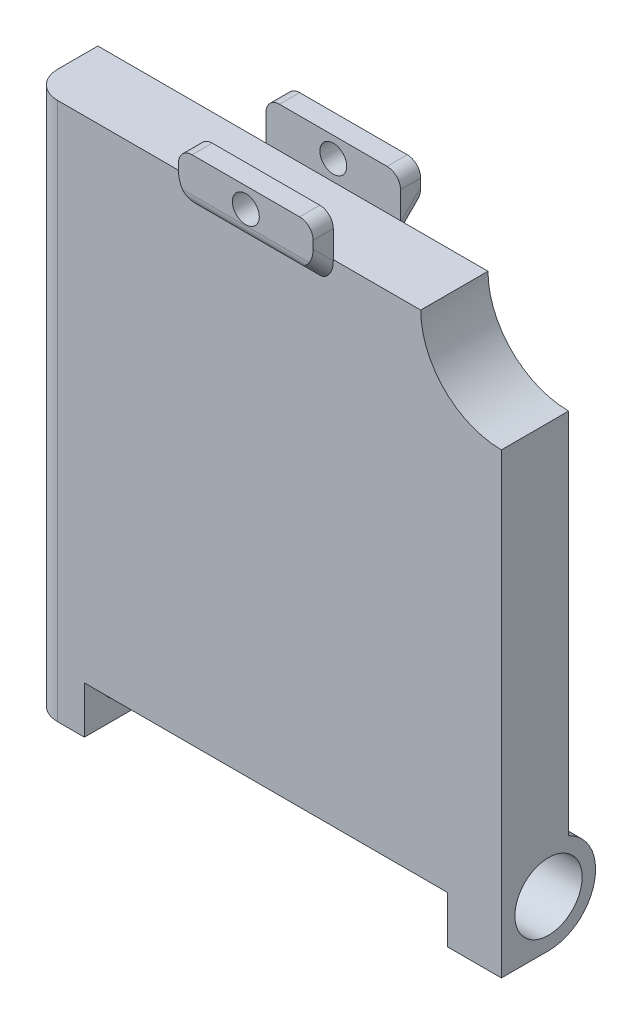
SolidWorks part; units mm, degrees
ref_plane "Front Plane" through (0, 0, 0) normal (0, 0, 1) x (1, 0, 0)
ref_plane "Top Plane" through (0, 0, 0) normal (0, 1, 0) x (1, 0, 0)
ref_plane "Right Plane" through (0, 0, 0) normal (1, 0, 0) x (0, 0, -1)
sketch "Sketch1" plane through (0, 0, 0) normal (0, 0, 1) x (1, 0, 0)
  line L0 (0, 0) -> (0, 36.5)
  line L1 (0, 36.5) -> (35, 36.5)
  line L2 (35, 36.5) -> (35, 0)
  line L3 (35, 0) -> (0, 0)
  dimension "D1" = 36.5
  dimension "D2" = 35
extrude "Boss-Extrude1" add sketch "Sketch1" along normal mid plane 5
sketch "Sketch3" plane through (35, 0, 0) normal (1, 0, 0) x (0, 0, -1)
  line L0 (-2.5, 5.8058) -> (-2.5, 2.251) construction
  line L2 (-2.5, 0) -> (-2.5, 36.5) construction
  line L3 (-2.5, 0) -> (2.5, 0) construction
  circle A0 centre (1, 0) radius 3.5
  dimension "D1" = 7
extrude "Cut-Extrude1" cut sketch "Sketch3" against normal up to surface (35 mm away) up to face at (0, 18.25, 0)
sketch "Sketch4" plane through (35, 0, 0) normal (1, 0, 0) x (0, 0, -1)
  line L0 (-2.5, 0) -> (-2.5, -3.5)
  line L1 (-2.5, -3.5) -> (1, -3.5)
  circle A0 centre (1, 0) radius 3.5
  arc A1 (2.5, 3.1623) -> (-2.5, 0) centre (1, 0) ccw construction
  circle A2 centre (1, 0) radius 2.5
  arc M4 (-2.5, 0) -> (2.5, 3.1623) centre (1, 0) cw
  dimension "D1" = 5
extrude "Boss-Extrude3" add sketch "Sketch4" against normal blind 4 contours A0 A2 M4 | A0 L0 L1 region at (35, -2.7182, 1.7182) region at (35, 2.8744, 0.8179)
ref_plane "Plane2" through (17.5, 0, 0) normal (1, 0, 0) x (0, 0, -1)
mirror "Mirror2" about plane through (17.5, 0, 0) normal (1, 0, 0) of "Boss-Extrude3"
sketch "Sketch5" plane through (17.5, 0, 0) normal (1, 0, 0) x (0, 0, -1)
  line L0 (2.5, 36.5) -> (4, 36.5)
  line L1 (-2.5, 36.5) -> (-4, 36.5)
  line L2 (-4, 36.5) -> (-2.5, 35)
  line L3 (-2.5, -3.5) -> (-2.5, 36.5) construction
  line L4 (4, 36.5) -> (2.5, 35)
  line L5 (2.5, 3.1623) -> (2.5, 36.5) construction
  line L6 (-4, 36.5) -> (-4, 39.5)
  line L7 (-4, 39.5) -> (-2.5, 39.5)
  line L8 (-2.5, 39.5) -> (-2.5, 36.5)
  line L9 (2.5, 36.5) -> (2.5, 39.5)
  line L10 (2.5, 39.5) -> (4, 39.5)
  line L11 (4, 39.5) -> (4, 36.5)
  line L12 (-2.5, 35) -> (-2.5, 36.5)
  line L13 (2.5, 35) -> (2.5, 36.5)
  dimension "D1" = 1.5
  dimension "D2" = 3
extrude "Boss-Extrude4" add sketch "Sketch5" along normal mid plane 10 contours L8 L7 L6 L1 | L2 L12 L1 | L13 L4 L0 | L11 L10 L9 L0 region at (17.5, 38, -3.25) region at (17.5, 36, -3) region at (17.5, 36, 3) region at (17.5, 38, 3.25)
sketch "Sketch6" plane through (0, 0, 4) normal (0, 0, 1) x (1, 0, 0)
  line L0 (17.5, 39.5) -> (17.5, 36.5) construction
  line L1 (22.5, 39.5) -> (12.5, 39.5) construction
  line L2 (22.5, 36.5) -> (12.5, 36.5) construction
  circle A0 centre (17.5, 38) radius 1
  point P8 (17.5, 38)
  dimension "D1" = 2
extrude "Cut-Extrude2" cut sketch "Sketch6" against normal up to surface (8 mm away) up to face at (17.5, 38, -4)
fillet "Fillet1" radius 1 6 edges at (12.5, 35.75, -3.25) (22.5, 35.75, -3.25) (17.5, 36.5, -4) (17.5, 36.5, 4) (12.5, 35.75, 3.25) (22.5, 35.75, 3.25)
fillet "Fillet2" radius 1 4 edges at (12.5, 39.5, -3.25) (12.5, 39.5, 3.25) (22.5, 39.5, -3.25) (22.5, 39.5, 3.25)
sketch "Sketch7" plane through (0, 0, 2.5) normal (0, 0, 1) x (1, 0, 0)
  circle A0 centre (35, 36.5) radius 6
  point P2 (0, 0)
  dimension "D1" = 12
extrude "Cut-Extrude3" cut sketch "Sketch7" against normal up to surface (5 mm away) up to face at (17.5, 25.0743, -2.5)
fillet "Fillet3" radius 2 1 edges at (0, 16.5, 2.5)
